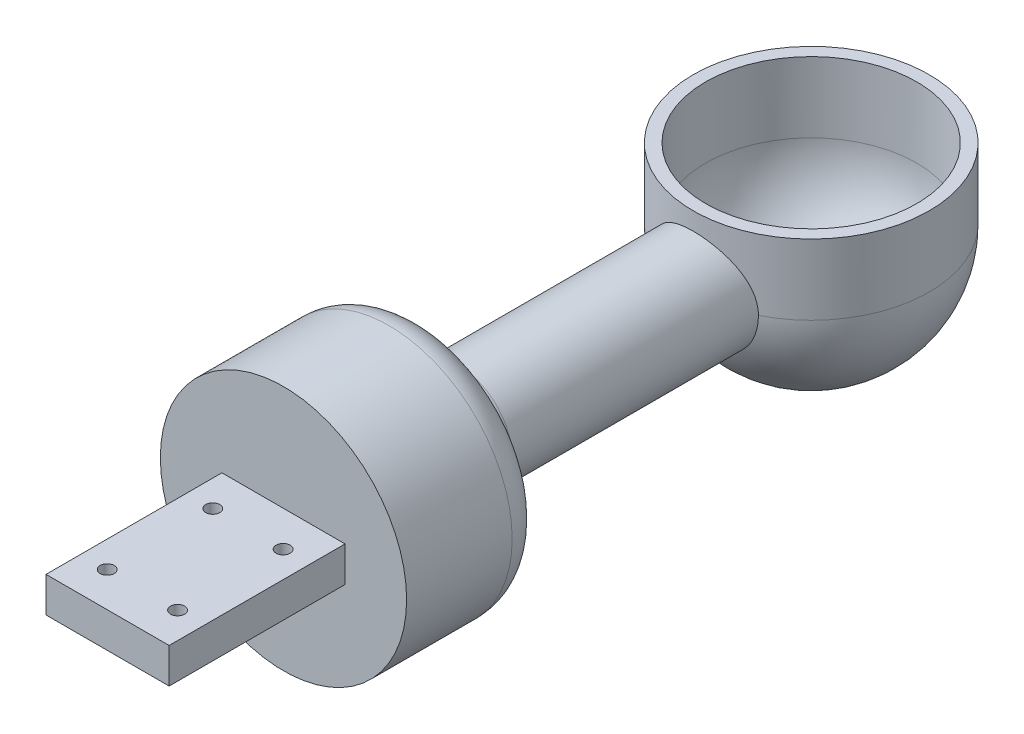
SolidWorks part; units mm, degrees
ref_plane "Front Plane" through (0, 0, 0) normal (0, 0, 1) x (1, 0, 0)
ref_plane "Top Plane" through (0, 0, 0) normal (0, 1, 0) x (1, 0, 0)
ref_plane "Right Plane" through (0, 0, 0) normal (1, 0, 0) x (0, 0, -1)
sketch "Sketch1" plane through (0, 0, 0) normal (0, 0, 1) x (1, 0, 0)
  circle A0 centre (0, 0) radius 35
  dimension "D1" = 70
extrude "Boss-Extrude1" add sketch "Sketch1" along normal blind 40
sketch "Sketch2" plane through (0, 0, 0) normal (0, 0, -1) x (-1, 0, 0)
  circle A0 centre (0, 0) radius 15
  dimension "D1" = 30
extrude "Boss-Extrude2" add sketch "Sketch2" along normal blind 80
fillet "Fillet1" radius 10 2 edges at (35, 0, 0) (-15, 0, 0)
sketch "Sketch3" plane through (0, 0, 0) normal (0, 1, 0) x (1, 0, 0)
  line L0 (-35, -40) -> (35, -40) construction
  line L1 (-17.5, -90) -> (17.5, -90)
  line L2 (-17.5, -90) -> (-17.5, -40)
  line L3 (-17.5, -40) -> (17.5, -40)
  line L4 (17.5, -90) -> (17.5, -40)
  line L6 (-10, -80.1) -> (10, -80.1) construction
  line L7 (-10, -80.1) -> (-10, -50.1) construction
  line L8 (-10, -50.1) -> (10, -50.1) construction
  line L9 (10, -80.1) -> (10, -50.1) construction
  line L10 (-10, -80.1) -> (10, -50.1) construction
  line L11 (-10, -50.1) -> (10, -80.1) construction
  circle A0 centre (-10, -50.1) radius 2
  circle A1 centre (10, -50.1) radius 2
  circle A2 centre (10, -80.1) radius 2
  circle A3 centre (-10, -80.1) radius 2
  point P0 (0, -40)
  point P11 (0, -65.1)
  point P18 (0, 0)
  dimension "D3" = 4
  dimension "D1" = 35
  dimension "D2" = 50
  dimension "D4" = 30
  dimension "D5" = 20
  dimension "D6" = 10.1
extrude "Boss-Extrude3" add sketch "Sketch3" along normal mid plane 10
sketch "Sketch4" plane through (0, 0, 0) normal (0, 1, 0) x (1, 0, 0)
  line L0 (0, 80) -> (0, 140) construction
  line L1 (15, 80) -> (-15, 80) construction
  line L2 (0, 140) -> (0, 143.541)
  line L3 (0, 80) -> (0, 76.459)
  arc A0 (0, 143.541) -> (0, 76.459) centre (0, 110) ccw
  arc A1 (0, 140) -> (0, 80) centre (0, 110) ccw
  dimension "D1" = 60
revolve "Revolve1" add sketch "Sketch4" angle 180 about L0 reverse direction yes
sketch "Sketch6" plane through (0, 0, 0) normal (0, 1, 0) x (1, 0, 0)
  circle A2 centre (0, 110) radius 30
  circle A3 centre (0, 110) radius 33.541
  arc A4 (15, 80) -> (-15, 80) centre (0, 110) ccw construction
  circle A5 centre (0, 110) radius 30 construction
extrude "Boss-Extrude4" add sketch "Sketch6" along normal blind 20
